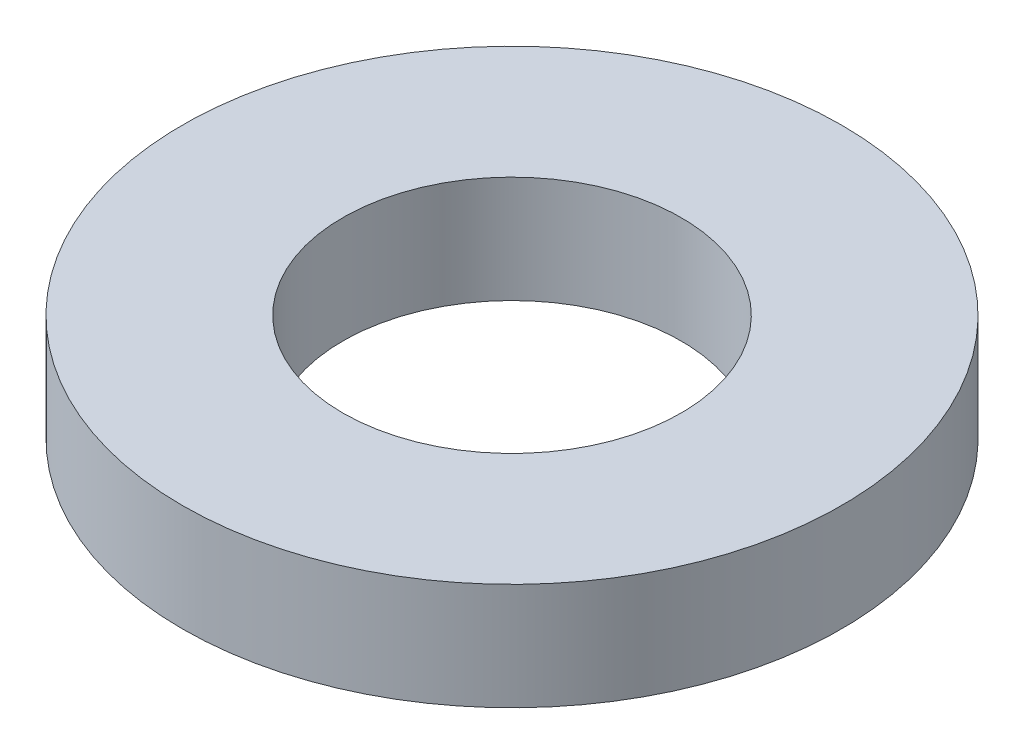
SolidWorks part; units mm, degrees
ref_plane "Front Plane" through (0, 0, 0) normal (0, 0, 1) x (1, 0, 0)
ref_plane "Top Plane" through (0, 0, 0) normal (0, 1, 0) x (1, 0, 0)
ref_plane "Right Plane" through (0, 0, 0) normal (1, 0, 0) x (0, 0, -1)
sketch "Sketch1" plane through (0, 0, 0) normal (0, 1, 0) x (1, 0, 0)
  circle A0 centre (0, 0) radius 92.5
  dimension "FLANGE_OD" = 185
extrude "Boss-Extrude1" add sketch "Sketch1" along normal blind 30
sketch "Sketch2" plane through (0, 0, 0) normal (0, 1, 0) x (1, 0, 0)
  circle A0 centre (0, 0) radius 47.5
  dimension "BORE_D" = 95
extrude "Cut-Extrude1" cut sketch "Sketch2" along normal through all
sketch "Sketch3" plane through (0, 30, 0) normal (0, 1, 0) x (1, 0, 0)
  circle A0 centre (0, 0) radius 34.7993 construction
  circle A1 centre (-34.7993, 0) radius 3.2488
  dimension "BOLT_D" = 6.4976
  dimension "BOLT_PCD" = 69.5986
extrude "Cut-Extrude2" cut sketch "Sketch3" against normal blind 27.2806 rebuild error yes
pattern_circular "CirPattern1" count 6 over 360 rebuild error yes
